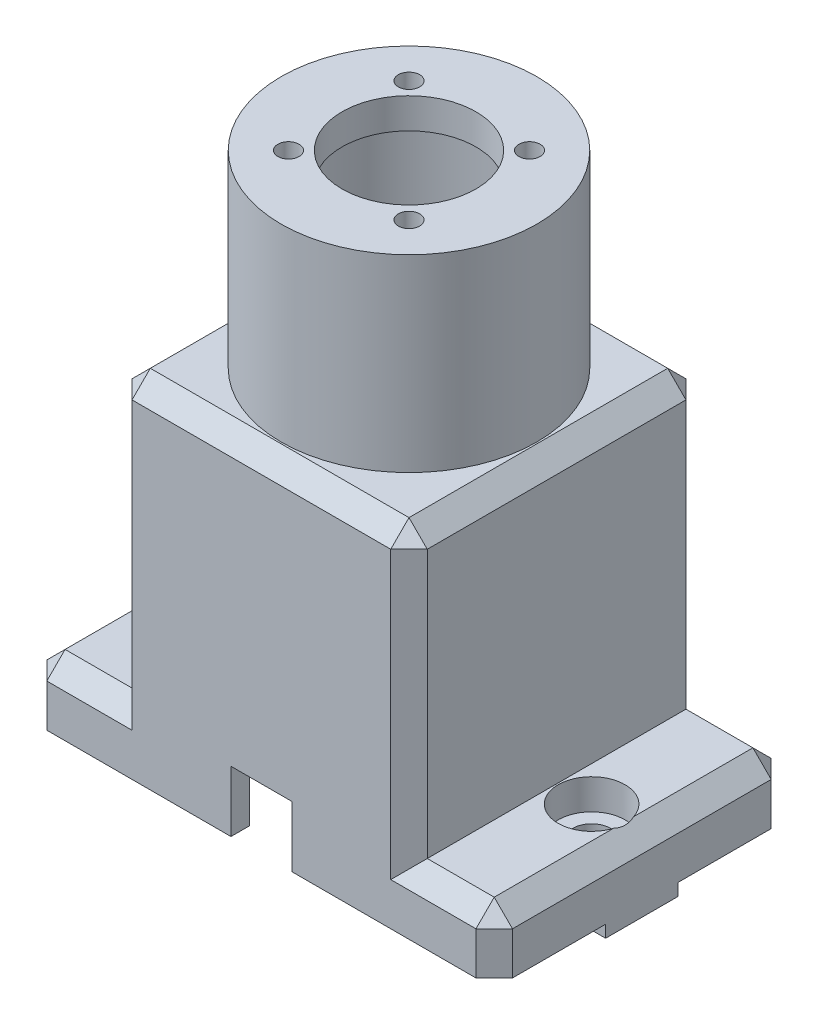
SolidWorks part; units mm, degrees
ref_plane "Płaszczyzna przednia" through (0, 0, 0) normal (0, 0, 1) x (1, 0, 0)
ref_plane "Płaszczyzna górna" through (0, 0, 0) normal (0, 1, 0) x (1, 0, 0)
ref_plane "Płaszczyzna prawa" through (0, 0, 0) normal (1, 0, 0) x (0, 0, -1)
sketch "Sketch1" plane through (0, 0, 0) normal (0, 1, 0) x (1, 0, 0)
  line L0 (0, 0) -> (0, -30.328) construction
  line L1 (0, 0) -> (19.9222, 19.9222) construction
  circle A0 centre (0, 0) radius 21
  circle A1 centre (0, 0) radius 14 construction
  circle A2 centre (-9.8995, -9.8995) radius 1.75
  circle A3 centre (-9.8995, 9.8995) radius 1.75
  circle A4 centre (9.8995, 9.8995) radius 1.75
  circle A5 centre (9.8995, -9.8995) radius 1.75
  point P19 (0, 0)
  dimension "D1" = 42
  dimension "D2" = 28
  dimension "D4" = 3.5
  dimension "D3" = 45
  dimension "D5" = 4
extrude "Boss-Extrude1" add sketch "Sketch1" along normal blind 31
sketch "Sketch3" plane through (0, 0, 0) normal (0, 1, 0) x (1, 0, 0)
  line L1 (24.25, -24.25) -> (-24.25, -24.25)
  line L2 (24.25, -24.25) -> (24.25, 24.25)
  line L3 (24.25, 24.25) -> (-24.25, 24.25)
  line L4 (-24.25, -24.25) -> (-24.25, 24.25)
  line L5 (24.25, -24.25) -> (-24.25, 24.25) construction
  line L6 (24.25, 24.25) -> (-24.25, -24.25) construction
  circle A0 centre (0, 0) radius 18.5
  point P0 (0, 0)
  dimension "D3" = 37
  dimension "D1" = 48.5
  dimension "D2" = 48.5
extrude "Boss-Extrude2" add sketch "Sketch3" against normal blind 57
sketch "Sketch4" plane through (0, 0, 0) normal (0, 1, 0) x (1, 0, 0)
  circle A0 centre (0, 0) radius 11
  dimension "D1" = 22
extrude "Cut-Extrude2" cut sketch "Sketch4" along normal through all both and the other way through all
sketch "Sketch5" plane through (0, 0, 0) normal (0, 0, 1) x (1, 0, 0)
  line L0 (-24.25, -57) -> (24.25, -57) construction
  line L1 (5, -67) -> (-5, -67)
  line L2 (5, -67) -> (5, -47)
  line L3 (5, -47) -> (-5, -47)
  line L4 (-5, -67) -> (-5, -47)
  line L5 (5, -67) -> (-5, -47) construction
  line L6 (5, -47) -> (-5, -67) construction
  point P0 (0, -57)
  dimension "D1" = 10
  dimension "D2" = 10
extrude "Cut-Extrude3" cut sketch "Sketch5" along normal through all
sketch "Sketch6" plane through (0, 0, 0) normal (0, 1, 0) x (1, 0, 0)
  line L0 (-24.25, 24.25) -> (-24.25, -24.25)
  line L8 (-24.25, 24.25) -> (-38.25, 24.25)
  line L9 (-24.25, -24.25) -> (-38.25, -24.25)
  line L10 (-38.25, 24.25) -> (-38.25, -24.25)
  line L11 (24.25, 24.25) -> (24.25, -24.25)
  line L12 (24.25, 24.25) -> (38.25, 24.25)
  line L13 (24.25, -24.25) -> (38.25, -24.25)
  line L14 (38.25, 24.25) -> (38.25, -24.25)
  dimension "D1" = 14
  dimension "D2" = 14
extrude "Boss-Extrude3" add sketch "Sketch6" along normal blind 10 from surface starting at face at (0, -57, 5.9764)
sketch "Sketch7" plane through (0, 0, 0) normal (0, 1, 0) x (1, 0, 0)
  line L0 (-38.25, -5.95) -> (38.25, -5.95)
  line L1 (-38.25, -5.95) -> (-38.25, 5.95)
  line L2 (38.25, -5.95) -> (38.25, 5.95)
  line L3 (-38.25, 5.95) -> (38.25, 5.95)
  line L4 (-38.25, 24.25) -> (-38.25, -24.25) construction
  line L5 (38.25, -24.25) -> (38.25, 24.25) construction
  dimension "D1" = 5.95
  dimension "D2" = 11.9
extrude "Boss-Extrude4" add sketch "Sketch7" against normal blind 2 from surface starting at face at (0, -57, 5.9764)
sketch "Sketch2" plane through (0, 0, 0) normal (0, 1, 0) x (1, 0, 0)
  circle A0 centre (0, 0) radius 18.5
  dimension "D1" = 37
extrude "Cut-Extrude1" cut sketch "Sketch2" along normal blind 26 and the other way through all
sketch "Sketch8" plane through (0, 0, 0) normal (0, 1, 0) x (1, 0, 0)
  line L0 (-37.7319, 0) -> (42.2681, 0) construction
  circle A0 centre (-30, 0) radius 3.1
  circle A1 centre (30, 0) radius 3.1
  dimension "D3" = 6.2
  dimension "D4" = 6.2
  dimension "D1" = 60
  dimension "D2" = 30
extrude "Cut-Extrude4" cut sketch "Sketch8" against normal through all
sketch "Sketch9" plane through (0, 0, 0) normal (0, 1, 0) x (1, 0, 0)
  circle A0 centre (-30, 0) radius 5.5
  circle A1 centre (30, 0) radius 5.5
  dimension "D1" = 11
  dimension "D2" = 11
extrude "Cut-Extrude5" cut sketch "Sketch9" against normal blind 5 from surface starting at face at (-30, -47, 3.1)
chamfer "Chamfer1" distance 3 angle 45 18 edges at (38.25, -52, 24.25) (38.25, -52, -24.25) (-38.25, -52, -24.25) (-38.25, -52, 24.25) (-31.25, -47, 24.25) (-38.25, -47, 0) (-31.25, -47, -24.25) (31.25, -47, -24.25) (38.25, -47, 0) (31.25, -47, 24.25) (24.25, 0, 0) (24.25, -23.5, 24.25) (0, 0, 24.25) (24.25, -23.5, -24.25) (0, 0, -24.25) (-24.25, -23.5, -24.25) (-24.25, 0, 0) (-24.25, -23.5, 24.25)
sketch "Sketch11" plane through (0, 0, 0) normal (0, 1, 0) x (1, 0, 0)
  line L1 (-21.25, -21.2) -> (21.25, -21.2)
  line L2 (-21.25, -21.2) -> (-21.25, 21.2)
  line L3 (-21.25, 21.2) -> (21.25, 21.2)
  line L4 (21.25, -21.2) -> (21.25, 21.2)
  line L5 (-21.25, -21.2) -> (21.25, 21.2) construction
  line L6 (-21.25, 21.2) -> (21.25, -21.2) construction
  point P0 (0, 0)
  dimension "D1" = 42.5
  dimension "D2" = 42.4
extrude "Cut-Extrude6" cut sketch "Sketch11" along normal blind 48 and the other way through all from surface starting at face at (-23.4556, -57, 16.8349)
